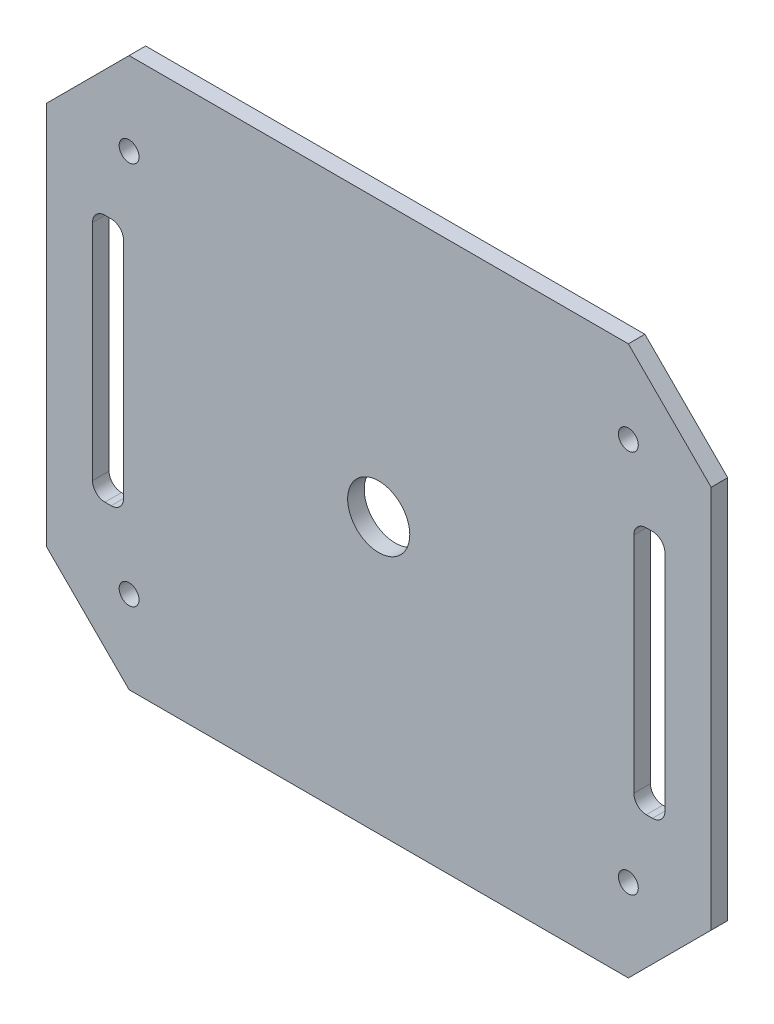
SolidWorks part; units mm, degrees
ref_plane "Front Plane" through (0, 0, 0) normal (0, 0, 1) x (1, 0, 0)
ref_plane "Top Plane" through (0, 0, 0) normal (0, 1, 0) x (1, 0, 0)
ref_plane "Right Plane" through (0, 0, 0) normal (1, 0, 0) x (0, 0, -1)
sketch "Sketch1" plane through (0, 0, 0) normal (0, 0, 1) x (1, 0, 0)
  line L0 (-14.8357, -38.0756) -> (0.1643, -23.0756)
  line L1 (0.1643, -23.0756) -> (90.5883, -23.0756)
  line L2 (90.5883, -23.0756) -> (105.5883, -38.0756)
  line L3 (-14.8357, -107.5446) -> (0.1643, -122.5446)
  line L4 (0.1643, -122.5446) -> (90.5883, -122.5446)
  line L5 (90.5883, -122.5446) -> (105.5883, -107.5446)
  line L6 (-14.8357, -38.0756) -> (-14.8357, -107.5446)
  line L7 (-4.2107, -50.3101) -> (-3.0857, -50.3101)
  line L8 (-6.4607, -52.5601) -> (-6.4607, -93.0601)
  line L9 (-4.2107, -95.3101) -> (-3.0857, -95.3101)
  line L10 (-0.8357, -52.5601) -> (-0.8357, -93.0601)
  line L11 (94.9633, -50.3101) -> (93.8383, -50.3101)
  line L12 (97.2133, -52.5601) -> (97.2133, -93.0601)
  line L13 (94.9633, -95.3101) -> (93.8383, -95.3101)
  line L14 (91.5883, -52.5601) -> (91.5883, -93.0601)
  line L15 (105.5883, -38.0756) -> (105.5883, -107.5446)
  arc A0 (97.2133, -52.5601) -> (94.9633, -50.3101) centre (94.9633, -52.5601) ccw
  arc A1 (93.8383, -50.3101) -> (91.5883, -52.5601) centre (93.8383, -52.5601) ccw
  arc A2 (94.9633, -95.3101) -> (97.2133, -93.0601) centre (94.9633, -93.0601) ccw
  arc A3 (91.5883, -93.0601) -> (93.8383, -95.3101) centre (93.8383, -93.0601) ccw
  arc A4 (-3.0857, -95.3101) -> (-0.8357, -93.0601) centre (-3.0857, -93.0601) ccw
  arc A5 (-6.4607, -93.0601) -> (-4.2107, -95.3101) centre (-4.2107, -93.0601) ccw
  arc A6 (-0.8357, -52.5601) -> (-3.0857, -50.3101) centre (-3.0857, -52.5601) ccw
  arc A7 (-4.2107, -50.3101) -> (-6.4607, -52.5601) centre (-4.2107, -52.5601) ccw
  circle A8 centre (0.1643, -38.0756) radius 1.8
  circle A9 centre (90.5883, -38.0756) radius 1.8
  circle A10 centre (90.5883, -107.5446) radius 1.8
  circle A11 centre (0.1643, -107.5446) radius 1.8
  circle A12 centre (45.3763, -72.8101) radius 5.625
  point P60 (91.5883, -72.8101)
  point P61 (-0.8357, -72.8101)
  point P62 (45.3763, -23.0756)
  point P64 (-14.8357, -72.8101)
  point P65 (105.5883, -72.8101)
  dimension "D1" = 90.424
  dimension "D2" = 69.469
  dimension "D3" = 15
  dimension "D4" = 15
  dimension "D5" = 15
  dimension "D6" = 15
  dimension "D7" = 40.5
  dimension "D8" = 49.7345
  dimension "D9" = 14
  dimension "D10" = 14
extrude "Boss-Extrude1" add sketch "Sketch1" along normal blind 3
